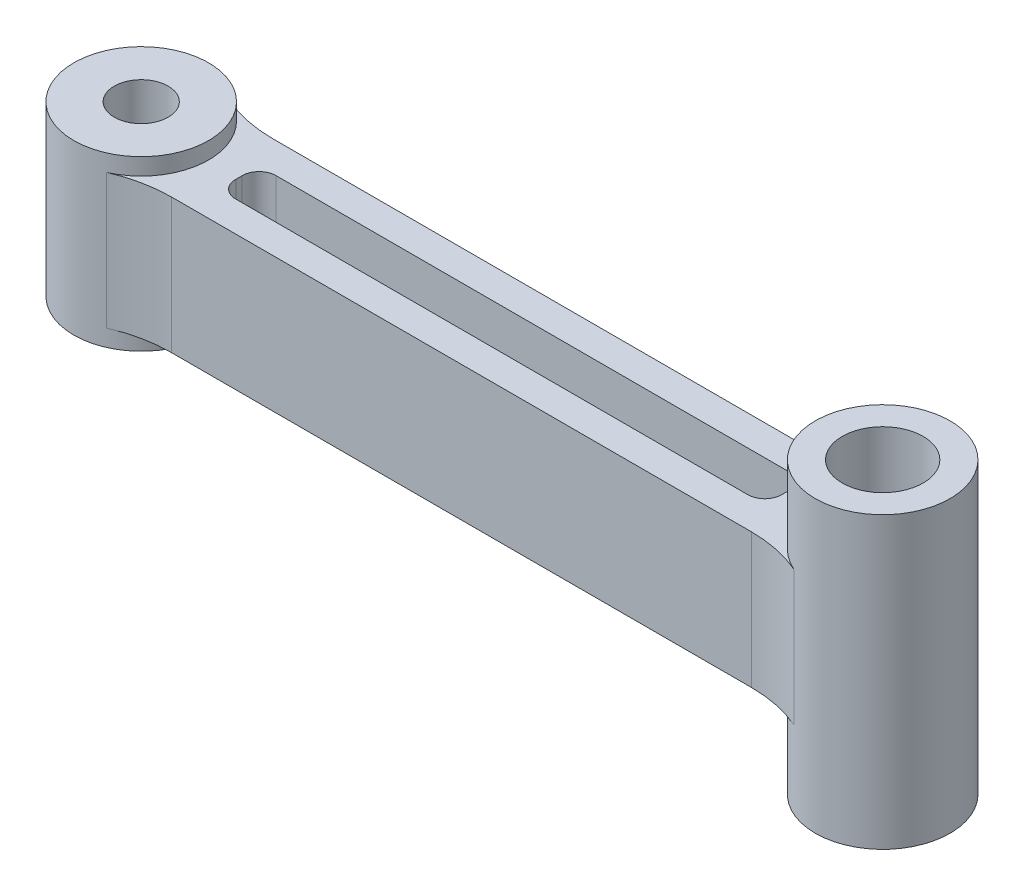
SolidWorks part; units mm, degrees
note: The reader was unsure of these and kept them because the rebuilt part matched: shared geometry of "Sketch2<3>".
ref_plane "Front Plane" through (0, 0, 0) normal (0, 0, 1) x (1, 0, 0)
ref_plane "Top Plane" through (0, 0, 0) normal (0, 1, 0) x (1, 0, 0)
ref_plane "Right Plane" through (0, 0, 0) normal (1, 0, 0) x (0, 0, -1)
sketch "Sketch2" plane through (0, 0, 0) normal (0, 1, 0) x (1, 0, 0)
  line L0 (0, 7.5) -> (-45, 7.5) construction
  line L1 (0, 0) -> (-48.3856, 0)
  line L2 (0, 0) -> (0, 15)
  line L3 (0, 15) -> (-48.3856, 15)
  circle A0 centre (-55, 7.5) radius 10
  circle A1 centre (-55, 7.5) radius 6
  dimension "D1" = 20
  dimension "D2" = 12
  dimension "D3" = 15
  dimension "D4" = 55
extrude "Boss-Extrude1" add sketch "Sketch2" along normal mid plane 43 contours A0 A1
extrude "Boss-Extrude2" add sketch "Sketch2<3>" along normal mid plane 20 contours L2 L0 A0 L1 | L0 L2 L3 A0
sketch "Sketch2<3>" plane through (0, 0, 0) normal (0, 1, 0) x (1, 0, 0) same geometry as "Sketch2"
mirror "Mirror1" about plane through (0, 10, 0) normal (-1, 0, 0) of bodies 102
sketch "Sketch3" plane through (0, 10, 0) normal (0, 1, 0) x (1, 0, 0)
  line L11 (48.3856, 10.5) -> (-48.3856, 10.5)
  line L12 (40.8137, 10.5) -> (-40.8137, 10.5)
  line L14 (48.3856, 4.5) -> (-48.3856, 4.5)
  line L15 (40.8137, 4.5) -> (-40.8137, 4.5)
  arc A4 (-45.4092, -3.375) -> (-45.4092, 18.375) centre (-55, 7.5) ccw
  arc A5 (-40.8137, 4.5) -> (-40.8137, 10.5) centre (-55, 7.5) ccw
  arc A7 (45.4092, 18.375) -> (45.4092, -3.375) centre (55, 7.5) ccw
  arc A8 (40.8137, 10.5) -> (40.8137, 4.5) centre (55, 7.5) ccw
  dimension "D1" = 4.5
  dimension "D2" = 4.5
  dimension "D3" = 4.5
  dimension "D4" = 4.5
extrude "Cut-Extrude1" cut sketch "Sketch3" against normal blind 6.25
mirror "Mirror2" about plane through (0, 0, 0) normal (0, 1, 0) of "Cut-Extrude1"
fillet "Fillet1" radius 20 4 edges at (48.3856, 0, 0) (48.3856, 0, -15) (-48.3856, 0, -15) (-48.3856, 0, 0)
fillet "Fillet2" radius 2.5 8 edges at (-40.8137, -6.875, -4.5) (-40.8137, -6.875, -10.5) (40.8137, -6.875, -4.5) (40.8137, -6.875, -10.5) (40.8137, 6.875, -10.5) (40.8137, 6.875, -4.5) (-40.8137, 6.875, -4.5) (-40.8137, 6.875, -10.5)
other "Move Face1" flip direction yes face at (-55, 21.5, -1.5) parameters "D1"=9
other "Move Face2" flip direction yes face at (-55, -21.5, -1.5) parameters "D1"=9
other "Move Face3" face at (-55, 12.5, -1.5) parameters "D1"=2
